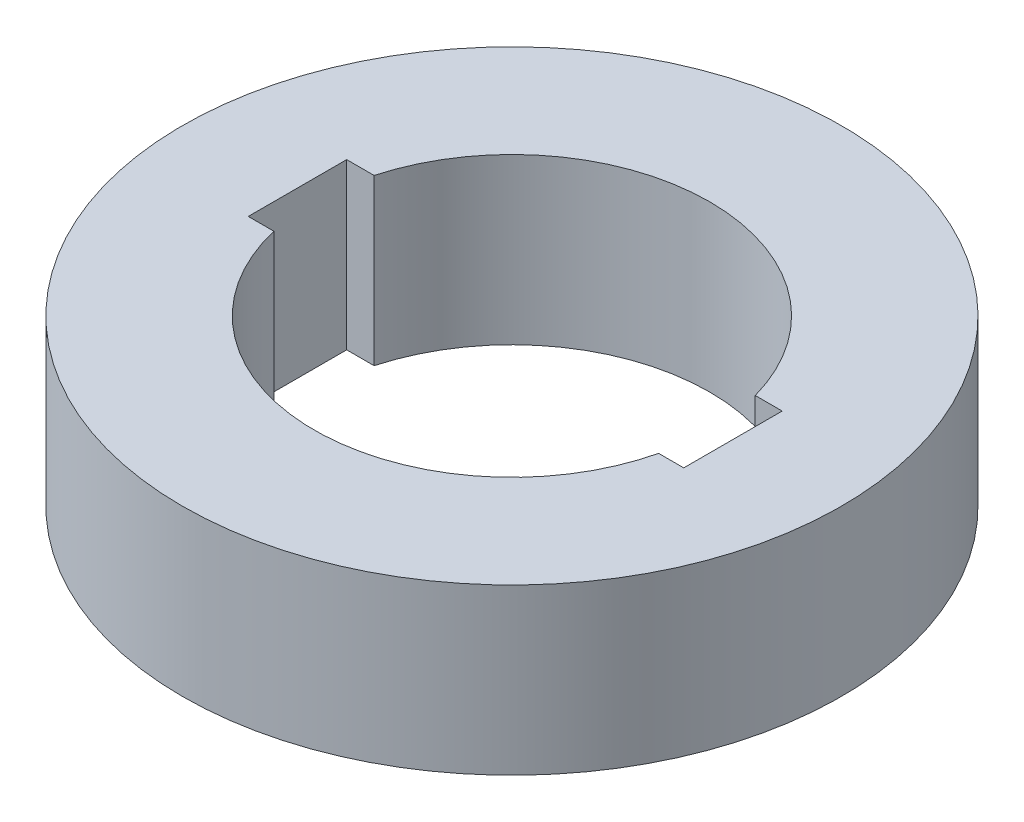
SolidWorks part; units mm, degrees
ref_plane "Front Plane" through (0, 0, 0) normal (0, 0, 1) x (1, 0, 0)
ref_plane "Top Plane" through (0, 0, 0) normal (0, 1, 0) x (1, 0, 0)
ref_plane "Right Plane" through (0, 0, 0) normal (1, 0, 0) x (0, 0, -1)
sketch "Sketch2" plane through (0, 0, 0) normal (0, 1, 0) x (1, 0, 0)
  line L0 (28.9137, 8) -> (33, 8)
  line L1 (-33.072, 8) -> (-28.9137, 8)
  line L2 (-33.072, 8) -> (-33.072, -6.9319)
  line L3 (-33.072, -6.9319) -> (-29.1882, -6.9319)
  line L4 (33, 8) -> (33, -6.9319)
  line L5 (29.1882, -6.9319) -> (33, -6.9319)
  circle A0 centre (0, 0) radius 50
  arc A1 (-29.1882, -6.9319) -> (29.1882, -6.9319) centre (0, 0) ccw
  arc A2 (28.9137, 8) -> (-28.9137, 8) centre (0, 0) ccw
  dimension "D1" = 100
  dimension "D2" = 60
  dimension "D3" = 8
  dimension "D4" = 33
extrude "Boss-Extrude1" add sketch "Sketch2" along normal blind 25
